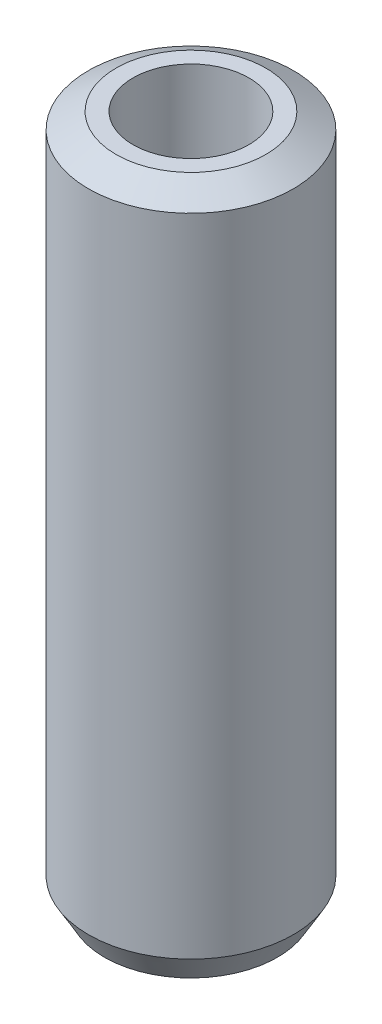
SolidWorks part; units mm, degrees
ref_plane "Front Plane" through (0, 0, 0) normal (0, 0, 1) x (1, 0, 0)
ref_plane "Top Plane" through (0, 0, 0) normal (0, 1, 0) x (1, 0, 0)
ref_plane "Right Plane" through (0, 0, 0) normal (1, 0, 0) x (0, 0, -1)
sketch "Sketch1" plane through (0, 0, 0) normal (0, 1, 0) x (1, 0, 0)
  circle A0 centre (0, 0) radius 37.5
  dimension "SHAFT_OD" = 75
extrude "Boss-Extrude1" add sketch "Sketch1" along normal blind 252.2904
sketch "Sketch2" plane through (0, 0, 0) normal (0, 1, 0) x (1, 0, 0)
  circle A0 centre (0, 0) radius 21.2043
  dimension "BORE_D" = 42.4086
extrude "Cut-Extrude1" cut sketch "Sketch2" along normal through all
chamfer "Chamfer1" distance 5.8244 angle 60 2 edges at (0, 252.2904, 37.5) (0, 0, 37.5) first distance on face at (0, 252.2904, 37.5) first distance on face at (0, 0, 21.2043)
